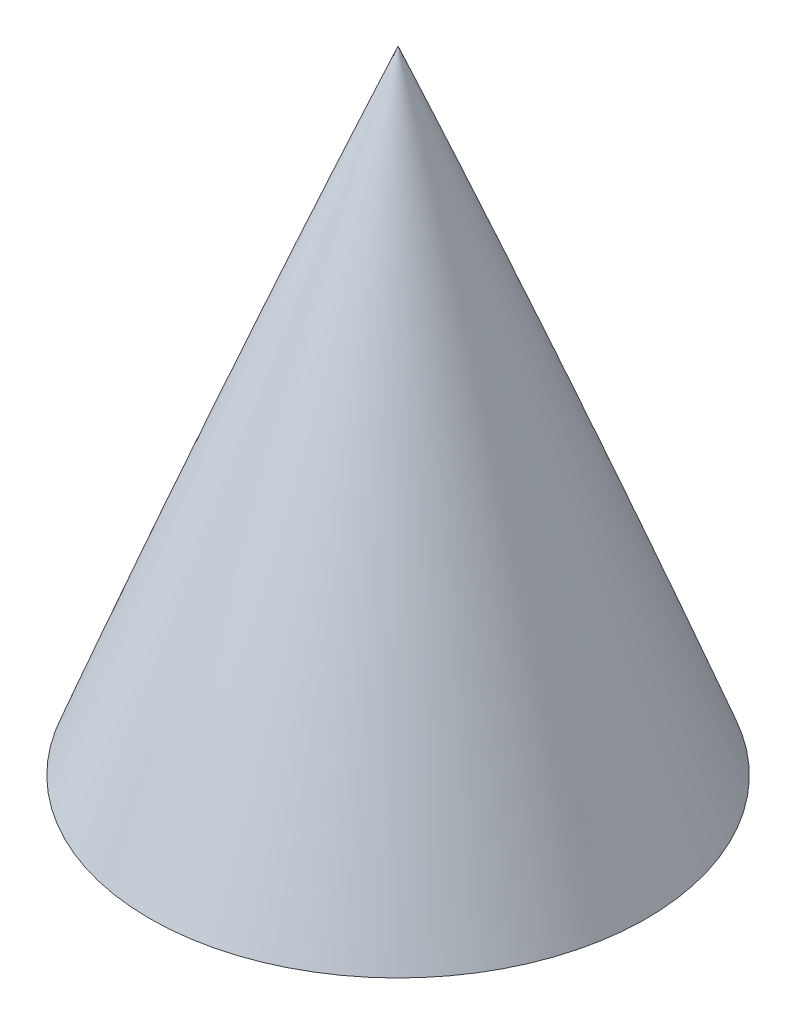
SolidWorks part; units mm, degrees
other "Markup1"
sketch "Sketch4" plane through (78.16, -154.2442, 78.16) normal (0.9651, -0.1718, 0.1975) x (-0.1686, -0.9851, -0.0334)
material "PE High Density Film"
ref_plane "Front Plane" through (0, 0, 0) normal (0, 0, 1) x (1, 0, 0)
ref_plane "Top Plane" through (0, 0, 0) normal (0, 1, 0) x (1, 0, 0)
ref_plane "Right Plane" through (0, 0, 0) normal (1, 0, 0) x (0, 0, -1)
sketch "Sketch1" plane through (0, 0, 0) normal (0, 0, 1) x (1, 0, 0)
  line L3 (0, 0) -> (0, 398.8705) construction
  line L6 (0, 400) -> (0, 402.7567)
  line L9 (0, 400) -> (0, 396.4892)
  line L10 (78.35, 0) -> (-964.0394, 0) construction
  line L11 (0, 411.0234) -> (0, 614.1078) construction
  line L14 (78.35, 0) -> (78.35, -150)
  line L15 (78.35, -150) -> (80.75, -150)
  line L16 (80.75, 0) -> (80.75, -150)
  arc A0 (78.35, 0) -> (0, 396.4892) centre (-964.0394, 0) ccw
  arc A1 (80.75, 0) -> (0, 402.7567) centre (-964.0394, 0) ccw
  circle A2 centre (-964.0394, 0) radius 1042.3894 construction
  circle A3 centre (-964.0394, 0) radius 1044.7894 construction
  point P11 (0, 400)
  dimension "D5" = 1042.3894
  dimension "D1" = 400
  dimension "D2" = 3.5108
  dimension "D3" = 2.4
  dimension "D4" = 78.35
  dimension "D6" = 150
  dimension "D7" = 2.4
revolve "Revolve3" add sketch "Sketch1" angle 360 about L6 reverse direction yes
sketch "Sketch5" plane through (0, -150, 0) normal (0, -1, 0) x (1, 0, 0)
  circle A0 centre (0, 0) radius 78.35
extrude "Boss-Extrude1" add sketch "Sketch5" against normal up to surface (150 mm away) separate body
delete or keep bodies "Body-Delete/Keep 1" type delete bodies bodies 101
ref_plane "Plane2" through (0, 396.4892, 0) normal (0, 1, 0) x (1, 0, 0)
ref_plane "Plane3" through (0, 366.4892, 0) normal (0, 1, 0) x (1, 0, 0)
split "Split1" trim tools "Plane3" bodies to split 109 resulting bodies 110 111
delete or keep bodies "Body-Delete/Keep 2" type delete bodies bodies 111
shell "Shell1" thickness 3 removed face at (0, 366.4892, 11.7994)
